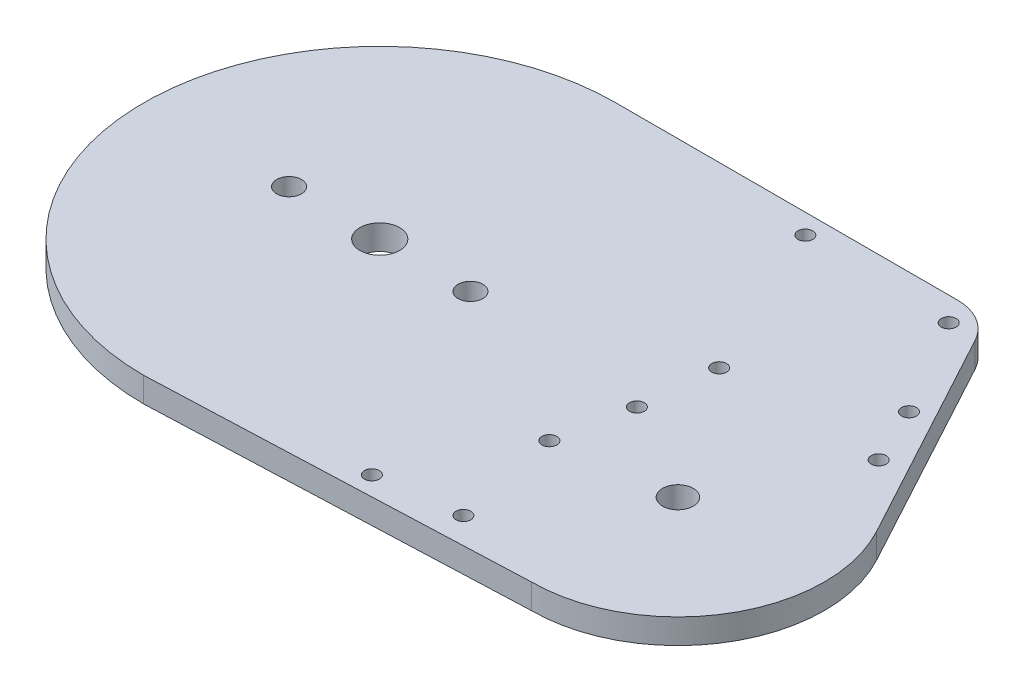
SolidWorks part; units mm, degrees
ref_plane "前视基准面" through (0, 0, 0) normal (0, 0, 1) x (1, 0, 0)
ref_plane "上视基准面" through (0, 0, 0) normal (0, 1, 0) x (1, 0, 0)
ref_plane "右视基准面" through (0, 0, 0) normal (1, 0, 0) x (0, 0, -1)
sketch "Sketch1" plane through (0, 0, 0) normal (0, 1, 0) x (1, 0, 0)
  line L0 (0, 0) -> (0, -15) construction
  line L1 (0, -15) -> (75, -15) construction
  line L2 (0, -47.5) -> (0, -44.5) construction
  line L3 (0, -44.5) -> (94.3585, -44.5) construction
  line L4 (0, -47.5) -> (75, -44.5)
  line L5 (0, 47.5) -> (68.764, 47.5)
  line L6 (77.559, 42.259) -> (100.9453, -0.9611)
  line L7 (0, 0) -> (75, -15) construction
  line L8 (75, -15) -> (55.1439, -3.3924) construction
  line L9 (73.1615, 44.8795) -> (73.8831, 46.0904) construction
  line L10 (73.8831, 46.0904) -> (71.8355, 42.6542) construction
  line L11 (68.764, 47.5) -> (77.559, 42.259) construction
  line L12 (73.1615, 44.8795) -> (68.764, 37.5) construction
  arc A0 (0, 47.5) -> (0, -47.5) centre (0, 0) ccw
  arc A2 (75, -44.5) -> (100.9453, -0.9611) centre (75, -15) ccw
  circle A3 centre (75.0001, 47.5) radius 7.5 construction
  arc A4 (77.559, 42.259) -> (68.764, 47.5) centre (68.764, 37.5) ccw
  circle A5 centre (0, 0) radius 4
  circle A12 centre (75, -15) radius 23 construction
  circle A15 centre (55.1439, -3.3924) radius 1.5
  circle A16 centre (52.2069, -18.0777) radius 1.5
  circle A17 centre (0, 0) radius 18.25 construction
  circle A18 centre (18.25, 0) radius 2.5
  circle A19 centre (-18.25, 0) radius 2.5
  circle A20 centre (75, -15) radius 3.1
  circle A21 centre (71.8355, 42.6542) radius 1.5
  circle A22 centre (83.3547, 23.1429) radius 1.5
  circle A23 centre (42.1373, 43.5) radius 1.5
  circle A24 centre (40.2934, -41.8851) radius 1.5
  circle A25 centre (56.5917, 11.711) radius 1.5
  circle A26 centre (88.688, 11.711) radius 1.5
  circle A27 centre (56.5917, -39.7686) radius 1.5
  point P28 (75, -15)
  dimension "D1" = 95
  dimension "D4" = 19
  dimension "D6" = 15
  dimension "D7" = 10
  dimension "D8" = 8
  dimension "D9" = 46
  dimension "D10" = 3
  dimension "D12" = 4
  dimension "D11" = 36.5
  dimension "D13" = 5
  dimension "D14" = 5
  dimension "D15" = 6.2
  dimension "D16" = 3
  dimension "D17" = 3
  dimension "D18" = 3
  dimension "D19" = 3
  dimension "D20" = 3
  dimension "D21" = 3
  dimension "D22" = 3
  dimension "D2" = 15
  dimension "D3" = 75
  dimension "D5" = 3
extrude "Boss-Extrude1" add sketch "Sketch1" along normal blind 5
